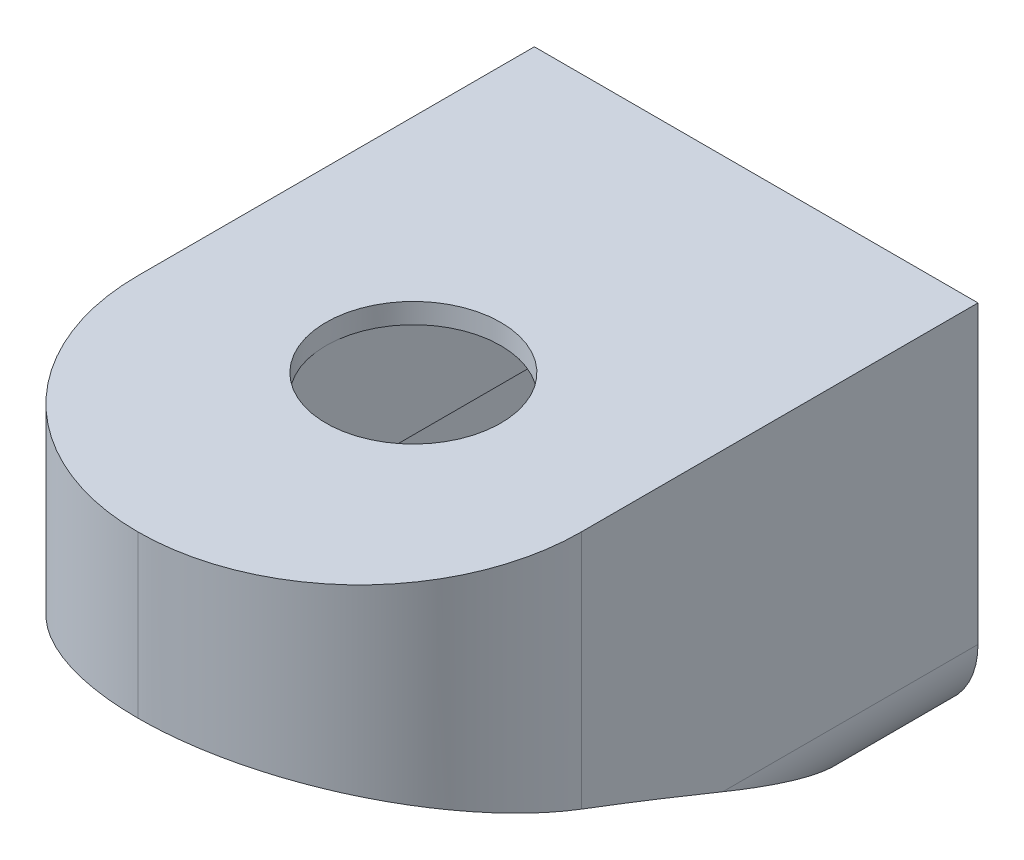
SolidWorks part; units mm, degrees
ref_plane "Front Plane" through (0, 0, 0) normal (0, 0, 1) x (1, 0, 0)
ref_plane "Top Plane" through (0, 0, 0) normal (0, 1, 0) x (1, 0, 0)
ref_plane "Right Plane" through (0, 0, 0) normal (1, 0, 0) x (0, 0, -1)
sketch "Sketch1" plane through (0, 0, 0) normal (0, 0, 1) x (1, 0, 0)
  line L1 (-16.5, -14) -> (16.5, -14)
  line L2 (-16.5, -14) -> (-16.5, 14)
  line L3 (-16.5, 14) -> (16.5, 14)
  line L4 (16.5, -14) -> (16.5, 14)
  line L5 (-16.5, -14) -> (16.5, 14) construction
  line L6 (-16.5, 14) -> (16.5, -14) construction
  point P0 (0, 0)
  dimension "D1" = 33
  dimension "D2" = 28
extrude "Boss-Extrude1" add sketch "Sketch1" along normal blind 46
sketch "Sketch3" plane through (16.5, 0, 0) normal (1, 0, 0) x (0, 0, -1)
  line L0 (-46, -14) -> (0, -14) construction
  line L1 (-46, -14) -> (-46, 14) construction
  line L2 (-46, 2) -> (-46, -14)
  line L3 (-46, -14) -> (-5, -14)
  line L4 (0, -14) -> (0, 14) construction
  spline S0 degree 2 poles (-5, -14) (-25.1197, -4.947) (-46, 2) knots 0 0 0 1 1 1
  dimension "D1" = 5
  dimension "D2" = 12
extrude "Cut-Extrude1" cut sketch "Sketch3" against normal through all
sketch "Sketch4" plane through (16.5, 0, 0) normal (1, 0, 0) x (0, 0, -1)
  line L0 (-5, -14) -> (-2.5, -14)
  line L1 (-5, -14) -> (0, -14) construction
  line L2 (-2.5, -14) -> (-2.5, 3.5)
  line L3 (-2.5, 3.5) -> (-40.5, 3.5)
  line L4 (-40.5, 3.5) -> (-40.5, 0.129)
  parabola Q0 (-5, -14) -> (-46, 2) focus (-109.0322, -204.8792) apex (-35.6074, -1.6051) construction
  parabola Q1 (-5, -14) -> (-46, 2) focus (-109.0322, -204.8792) apex (-35.6074, -1.6051) construction
  parabola Q2 (-5, -14) -> (-40.5, 0.129) focus (-109.0322, -204.8792) apex (-35.6074, -1.6051)
  dimension "D1" = 17.5
  dimension "D2" = 38
extrude "Cut-Extrude4" cut sketch "Sketch4" against normal blind 27 from offset 3 offset against normal yes
fillet "Fillet1" radius 12.5 2 edges at (13.5, 1.8145, 40.5) (-13.5, 1.8145, 40.5)
fillet "Fillet2" radius 16.5 2 edges at (-16.5, 8, 46) (16.5, 8, 46)
fillet "Fillet3" radius 6 2 edges at (-16.5, -14, 2.5) (16.5, -14, 2.5)
sketch "Sketch5" plane through (0, 3.5, 0) normal (0, -1, 0) x (1, 0, 0)
  line L0 (0, 0) -> (0, 46) construction
  line L1 (-10.5, 2.5) -> (10.5, 2.5) construction
  line L2 (6.5, 9) -> (-6.5, 9)
  line L3 (6.5, 9) -> (6.5, 32)
  line L4 (6.5, 32) -> (-6.5, 32)
  line L5 (-6.5, 9) -> (-6.5, 32)
  line L6 (6.5, 9) -> (-6.5, 32) construction
  line L7 (6.5, 32) -> (-6.5, 9) construction
  point P4 (0, 20.5)
  dimension "D1" = 6.5
  dimension "D2" = 23
  dimension "D3" = 13
extrude "Cut-Extrude8" cut sketch "Sketch5" against normal blind 9
sketch "Sketch6" plane through (0, 12.5, 0) normal (0, -1, 0) x (1, 0, 0)
  line L0 (0, 32) -> (0, 9) construction
  line L1 (6.5, 32) -> (-6.5, 32) construction
  line L2 (-6.5, 9) -> (6.5, 9) construction
  line L3 (6.5, 32) -> (-6.5, 32) construction
  circle A0 centre (0, 25.5) radius 6.5
  dimension "D1" = 13
extrude "Cut-Extrude9" cut sketch "Sketch6" against normal through all
sketch "Sketch7" plane through (0, 3.5, 0) normal (0, -1, 0) x (1, 0, 0)
  line L0 (-6.5, 20.5) -> (6.5, 20.5) construction
  line L1 (-6.5, 32) -> (-6.5, 9) construction
  line L2 (6.5, 9) -> (6.5, 32) construction
  line L3 (0, 6.7) -> (0, 34.3) construction
  circle A0 centre (0, 34.3) radius 1
  circle A1 centre (0, 6.7) radius 1
  point P10 (0, 20.5)
  dimension "D2" = 2
  dimension "D1" = 27.6
extrude "Cut-Extrude10" cut sketch "Sketch7" against normal blind 8
sketch "Sketch8" plane through (0, 0, 0) normal (0, 0, -1) x (-1, 0, 0)
  line L0 (0, 0) -> (-21.203, 0) construction
  line L1 (-16.5, -8) -> (-16.5, 14) construction
  circle A0 centre (-9.5, 0) radius 0.9251
  circle A1 centre (-5, 0) radius 2.5
  circle A2 centre (-0.5, 0) radius 0.9251
  dimension "D1" = 1.8501
  dimension "D2" = 5
  dimension "D3" = 9
  dimension "D4" = 4.5
  dimension "D5" = 11.5
extrude "Cut-Extrude11" cut sketch "Sketch8" against normal up to surface (2.5 mm away) up to face at (0, -7.9645, 2.5)
